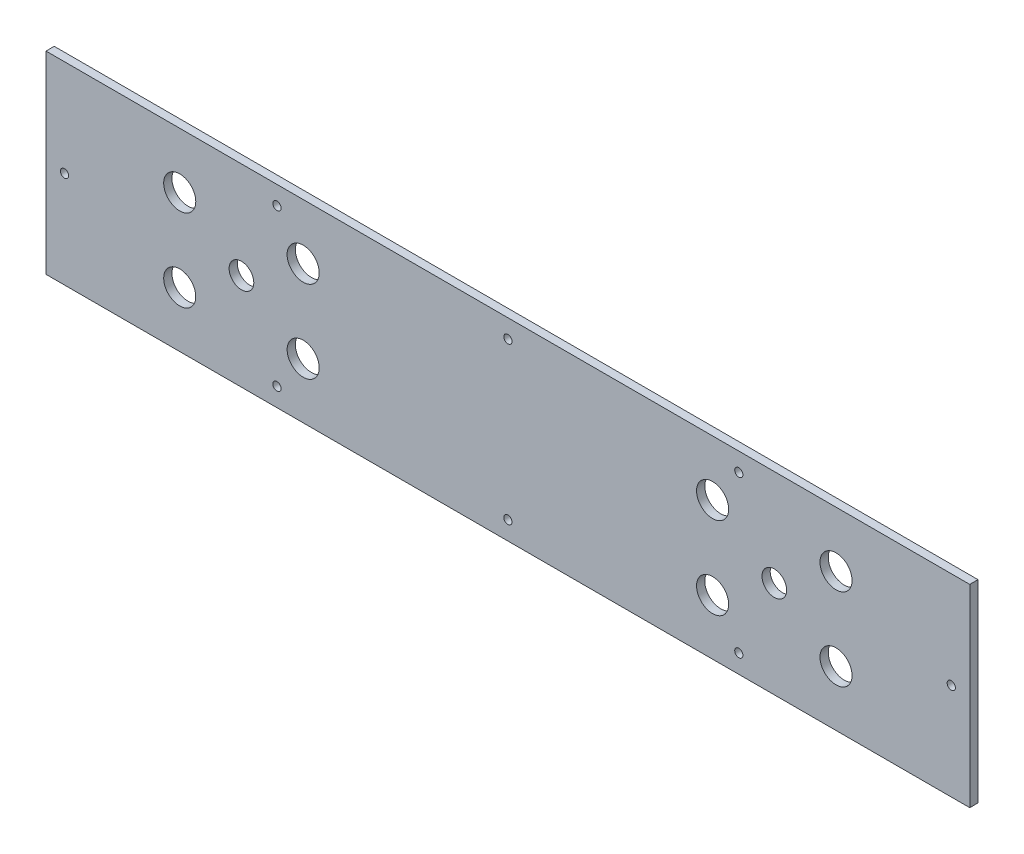
SolidWorks part; units mm, degrees
ref_plane "Piano frontale" through (0, 0, 0) normal (0, 0, 1) x (1, 0, 0)
ref_plane "Piano superiore" through (0, 0, 0) normal (0, 1, 0) x (1, 0, 0)
ref_plane "Piano destro" through (0, 0, 0) normal (1, 0, 0) x (0, 0, -1)
sketch "Schizzo1" plane through (0, 0, 0) normal (0, 0, 1) x (1, 0, 0)
  line L0 (-224.5, 351.6275) -> (-224.5, -66.2585) construction
  line L1 (0, 0) -> (-449, 0)
  line L2 (0, 0) -> (0, 94)
  line L3 (0, 94) -> (-449, 94)
  line L4 (-449, 0) -> (-449, 94)
  line L5 (-384, 47) -> (120.8821, 47) construction
  line L6 (-476.1211, 67) -> (22.7405, 67) construction
  line L7 (-476.1211, 27) -> (22.7405, 27) construction
  line L8 (-354, 67) -> (-354, 27) construction
  line L9 (-224.5, 94) -> (-449, 0) construction
  line L10 (-336.75, 47) -> (-336.75, 0) construction
  line L11 (-95, 67) -> (-95, 27) construction
  circle A0 centre (-384, 27) radius 7.8
  circle A1 centre (-9, 47) radius 2
  circle A2 centre (-224.5, 85) radius 2
  circle A3 centre (-440, 47) radius 2
  circle A4 centre (-224.5, 9) radius 2
  circle A5 centre (-324, 27) radius 7.8
  circle A6 centre (-324, 67) radius 7.8
  circle A7 centre (-336.75, 85) radius 2
  circle A8 centre (-384, 67) radius 7.8
  circle A9 centre (-336.75, 9) radius 2
  circle A10 centre (-112.25, 9) radius 2
  circle A11 centre (-112.25, 85) radius 2
  circle A12 centre (-65, 67) radius 7.8
  circle A13 centre (-65, 27) radius 7.8
  circle A14 centre (-125, 27) radius 7.8
  circle A15 centre (-125, 67) radius 7.8
  circle A16 centre (-354, 47) radius 6
  circle A17 centre (-95, 47) radius 6
  point P9 (-224.5, 47)
  dimension "D3" = 4
  dimension "D2" = 4
  dimension "D5" = 65
  dimension "D8" = 4
  dimension "D9" = 9
  dimension "D10" = 15.6
  dimension "D12" = 15.6
  dimension "D14" = 15.6
  dimension "D17" = 12
  dimension "D18" = 12
  dimension "D1" = 449
  dimension "314" = 94
  dimension "D4" = 9
  dimension "D6" = 9
  dimension "D7" = 30
  dimension "D11" = 20
  dimension "D13" = 65
  dimension "D15" = 95
  dimension "D16" = 95
extrude "Estrusione-Estrusione1" add sketch "Schizzo1" along normal blind 4
